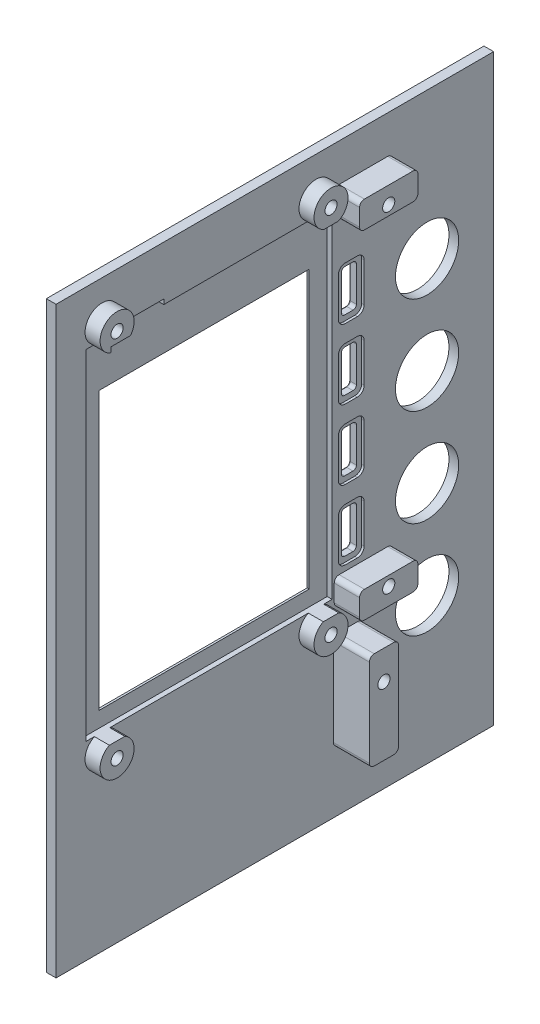
SolidWorks part; units mm, degrees
ref_plane "Front Plane" through (0, 0, 0) normal (0, 0, 1) x (1, 0, 0)
ref_plane "Top Plane" through (0, 0, 0) normal (0, 1, 0) x (1, 0, 0)
ref_plane "Right Plane" through (0, 0, 0) normal (1, 0, 0) x (0, 0, -1)
ref_plane "Plane2" through (-1175.0441, 0, 0) normal (-1, 0, 0) x (0, 0, 1)
sketch "Sketch2" plane through (-1175.0441, 0, 0) normal (-1, 0, 0) x (0, 0, 1)
  line L0 (-1293.9703, -887.0459) -> (-1293.9703, -787.0459) construction
  line L1 (-1208.9703, -777.0459) -> (-1298.9703, -777.0459)
  line L2 (-1208.9703, -777.0459) -> (-1208.9703, -897.0459)
  line L3 (-1208.9703, -897.0459) -> (-1298.9703, -897.0459)
  line L4 (-1298.9703, -777.0459) -> (-1298.9703, -897.0459)
  line L5 (-1293.9703, -887.0459) -> (-1292.4603, -887.0459) construction
  line L6 (-1293.9703, -787.0459) -> (-1292.4603, -787.0459) construction
  circle A0 centre (-1285.2753, -867.0459) radius 6.5
  circle A1 centre (-1285.2753, -847.0459) radius 6.5
  circle A2 centre (-1285.2753, -827.0459) radius 6.5
  circle A3 centre (-1285.2753, -807.0459) radius 6.5
  ellipse E0 centre (-1285.2753, -867.0459) end of major axis (-1284.8157, -867.5055) minor radius 0.65 construction
  ellipse E1 centre (-1285.2753, -847.0459) end of major axis (-1284.8157, -847.5055) minor radius 0.65 construction
  ellipse E2 centre (-1285.2753, -827.0459) end of major axis (-1284.8157, -827.5055) minor radius 0.65 construction
  ellipse E3 centre (-1285.2753, -807.0459) end of major axis (-1284.8157, -807.5055) minor radius 0.65 construction
  ellipse E4 centre (-1285.2753, -867.0459) end of major axis (-1284.8157, -867.5055) minor radius 0.65
  ellipse E5 centre (-1285.2753, -847.0459) end of major axis (-1284.8157, -847.5055) minor radius 0.65 construction
  ellipse E6 centre (-1285.2753, -827.0459) end of major axis (-1284.8157, -827.5055) minor radius 0.65
  ellipse E7 centre (-1285.2753, -807.0459) end of major axis (-1284.8157, -807.5055) minor radius 0.65
  dimension "D5" = 13
  dimension "D6" = 13
  dimension "D7" = 13
  dimension "D8" = 13
  dimension "D1" = 5
  dimension "D2" = 10
  dimension "D3" = 10
  dimension "D4" = 90
extrude "Boss-Extrude2" add sketch "Sketch2" along normal blind 2 contours L1 L4 L3 L2 A3 A2 A1 A0 region at (-1175.0441, -837.0459, -1252.3518)
sketch "Sketch3" plane through (-1177.0441, 0, 0) normal (-1, 0, 0) x (0, 0, 1)
  line L12 (-1218.8332, -854.8056) -> (-1262.0332, -854.8056) construction
  line L13 (-1262.0332, -854.8056) -> (-1262.0332, -797.8256) construction
  line L14 (-1218.8332, -797.8256) -> (-1218.8332, -854.8056) construction
  line L15 (-1262.0332, -797.8256) -> (-1218.8332, -797.8256) construction
  line L16 (-1218.8332, -854.8056) -> (-1262.0332, -854.8056)
  line L17 (-1262.0332, -854.8056) -> (-1262.0332, -797.8256)
  line L18 (-1218.8332, -797.8256) -> (-1218.8332, -854.8056)
  line L19 (-1262.0332, -797.8256) -> (-1218.8332, -797.8256)
extrude "tft_cutout" cut sketch "Sketch3" against normal through all
sketch "tft_inset_cutout" plane through (-1175.0441, 0, 0) normal (1, 0, 0) x (0, 0, -1)
  line L4 (1215.6332, -788.6846) -> (1215.6332, -857.4846) construction
  line L5 (1265.2332, -788.6846) -> (1215.6332, -788.6846) construction
  line L12 (1265.2332, -857.4846) -> (1265.2332, -788.6846) construction
  line L17 (1215.6332, -857.4846) -> (1265.2332, -857.4846) construction
  line L18 (1265.2332, -857.4846) -> (1265.2332, -788.6846) construction
  line L19 (1215.6332, -857.4846) -> (1265.2332, -857.4846) construction
  line L20 (1215.6332, -788.6846) -> (1215.6332, -857.4846) construction
  line L21 (1265.2332, -788.6846) -> (1215.6332, -788.6846) construction
  line L22 (1265.7332, -788.1846) -> (1215.1332, -788.1846)
  line L26 (1217.1332, -788.6846) -> (1231.1332, -788.6846)
  line L27 (1217.1332, -788.6846) -> (1217.1332, -787.1846)
  line L28 (1217.1332, -787.1846) -> (1231.1332, -787.1846)
  line L29 (1231.1332, -788.6846) -> (1231.1332, -787.1846)
  line L30 (1215.1332, -788.1846) -> (1215.1332, -857.9846)
  line L31 (1215.1332, -857.9846) -> (1265.7332, -857.9846)
  line L32 (1265.7332, -857.9846) -> (1265.7332, -788.1846)
  line M40 (1262.0332, -854.8056) -> (1218.8332, -854.8056)
  line M41 (1218.8332, -854.8056) -> (1218.8332, -797.8256)
  line M42 (1218.8332, -797.8256) -> (1262.0332, -797.8256)
  line M43 (1262.0332, -797.8256) -> (1262.0332, -854.8056)
  dimension "D3" = 1.5
  dimension "D4" = 0.5
  dimension "D1" = 14
  dimension "D2" = 1.5
extrude "Cut-Extrude2" cut sketch "tft_inset_cutout" against normal up to surface (1 mm away) contours L18 | L31 L32 L22 L29 L26 L27 L30 M43 M40 M41 M42 | L26 L29 L22 L27 | L22 L29 L28 L27 region at (-1175.0441, -823.0846, -1264.8711) region at (-1175.0441, -788.4346, -1224.1332) region at (-1175.0441, -787.6846, -1224.1332)
chamfer "Chamfer2" distance 1 angle 30 4 edges at (-1177.0441, -826.3156, -1262.0332) (-1177.0441, -854.8056, -1240.4332) (-1177.0441, -826.3156, -1218.8332) (-1177.0441, -797.8256, -1240.4332) first distance on face at (-1177.0441, -826.3156, -1240.4332)
sketch "Sketch6" plane through (-1175.0441, 0, 0) normal (1, 0, 0) x (0, 0, -1)
  line L5 (1266.1832, -859.8139) -> (1278.1832, -859.8139)
  line L6 (1266.1832, -859.8139) -> (1266.1832, -854.3139)
  line L7 (1266.1832, -854.3139) -> (1278.1832, -854.3139)
  line L8 (1266.1832, -859.8139) -> (1278.1832, -859.8139)
  line L9 (1278.1832, -859.8139) -> (1278.1832, -784.8139)
  line L10 (1278.1832, -784.8139) -> (1266.1832, -784.8139)
  line L11 (1266.1832, -784.8139) -> (1266.1832, -859.8139)
  line L12 (1266.1832, -859.8139) -> (1278.1832, -859.8139) construction
  line L13 (1278.1832, -859.8139) -> (1278.1832, -784.8139) construction
  line L14 (1278.1832, -784.8139) -> (1266.1832, -784.8139) construction
  line L15 (1266.1832, -784.8139) -> (1266.1832, -859.8139) construction
  line L16 (1278.1832, -859.8139) -> (1278.1832, -854.3139)
  line L17 (1266.1832, -784.8139) -> (1278.1832, -784.8139)
  line L18 (1266.1832, -784.8139) -> (1266.1832, -790.3139)
  line L19 (1266.1832, -790.3139) -> (1278.1832, -790.3139)
  line L20 (1278.1832, -784.8139) -> (1278.1832, -790.3139)
  circle A0 centre (1272.1832, -856.3139) radius 1.25 construction
  circle A1 centre (1272.1832, -856.3139) radius 1.25 construction
  circle A2 centre (1272.1832, -856.3139) radius 1.25
  circle A3 centre (1272.1832, -788.3139) radius 1.25 construction
  circle A4 centre (1272.1832, -788.3139) radius 1.25 construction
  circle A5 centre (1272.1832, -788.3139) radius 1.25
  dimension "D2" = 2.5
  dimension "D4" = 2.5
  dimension "D3" = 2
  dimension "D5" = 2
extrude "menu_standoffs" add sketch "Sketch6" along normal up to surface (5.203 mm away)
fillet "Fillet1" radius 1 8 edges at (-1172.4426, -790.3139, -1266.1832) (-1172.4426, -790.3139, -1278.1832) (-1172.4426, -784.8139, -1278.1832) (-1172.4426, -784.8139, -1266.1832) (-1172.4426, -854.3139, -1278.1832) (-1172.4426, -854.3139, -1266.1832) (-1172.4426, -859.8139, -1266.1832) (-1172.4426, -859.8139, -1278.1832)
sketch "Sketch7" plane through (-1169.8411, 0, 0) normal (1, 0, 0) x (0, 0, -1)
  circle A0 centre (1272.1832, -856.3139) radius 1.25 construction
  circle A1 centre (1272.1832, -788.3139) radius 1.25 construction
  circle A2 centre (1272.1832, -856.3139) radius 1.25
  circle A3 centre (1272.1832, -788.3139) radius 1.25
extrude "menu_standoff_holes" [suppressed] cut sketch "Sketch7" against normal blind 5 contours A2
sketch "Sketch8" plane through (-1175.0441, 0, 0) normal (1, 0, 0) x (0, 0, -1)
  circle A0 centre (1218.4332, -861.1056) radius 1.55 construction
  circle A1 centre (1262.4332, -861.1056) radius 1.55 construction
  circle A2 centre (1262.4332, -785.0256) radius 1.55 construction
  circle A3 centre (1218.4332, -785.0258) radius 1.55 construction
  circle A4 centre (1218.4332, -861.1056) radius 1.55 construction
  circle A5 centre (1262.4332, -861.1056) radius 1.55 construction
  circle A6 centre (1262.4332, -785.0256) radius 1.55 construction
  circle A7 centre (1218.4332, -785.0258) radius 1.55 construction
  circle A8 centre (1218.4332, -785.0258) radius 3.5
  circle A9 centre (1262.4332, -785.0256) radius 3.5
  circle A10 centre (1262.4332, -861.1056) radius 3.5
  circle A11 centre (1218.4332, -861.1056) radius 3.5
  circle A12 centre (1218.4332, -785.0258) radius 1.25
  circle A13 centre (1218.4332, -861.1056) radius 1.25
  circle A14 centre (1262.4332, -861.1056) radius 1.25
  circle A15 centre (1262.4332, -785.0256) radius 1.25
  dimension "D2" = 2.5
  dimension "D1" = 7
extrude "TFT_standoffs" add sketch "Sketch8" along normal up to surface (3.09 mm away)
sketch "Sketch9" plane through (-1175.0441, 0, 0) normal (1, 0, 0) x (0, 0, -1)
  circle A0 centre (1218.4332, -785.0258) radius 1.25 construction
  circle A1 centre (1218.4332, -861.1056) radius 1.25 construction
  circle A2 centre (1262.4332, -861.1056) radius 1.25 construction
  circle A3 centre (1262.4332, -785.0256) radius 1.25 construction
  circle A4 centre (1218.4332, -785.0258) radius 1.25
  circle A5 centre (1218.4332, -861.1056) radius 1.25
  circle A6 centre (1262.4332, -861.1056) radius 1.25
  circle A7 centre (1262.4332, -785.0256) radius 1.25
extrude "TFT_standoff_holes" cut sketch "Sketch9" against normal offset from surface (1 mm away) 1 up to face at (-1177.0441, -826.3156, -1240.4332)
extrude "Cut-Extrude5" cut sketch "Sketch5<3>" along normal through all contours L31 L32 L22 L29 L26 L27 L30 M43 M40 M41 M42 | L22 L29 L28 L27 | L26 L29 L22 L27 region at (-1175.0441, -823.0846, -1264.8711) region at (-1175.0441, -788.4346, -1224.1332) region at (-1175.0441, -787.6846, -1224.1332)
sketch "Sketch5<3>" plane through (-1175.0441, 0, 0) normal (1, 0, 0) x (0, 0, -1) same geometry as "tft_inset_cutout"
sketch "Sketch10" plane through (-1175.0441, 0, 0) normal (1, 0, 0) x (0, 0, -1)
  line L0 (1271.9367, -800.8206) -> (1271.9367, -808.8206) construction
  line L1 (1270.9367, -809.8206) -> (1268.4367, -809.8206) construction
  line L2 (1267.4367, -808.8206) -> (1267.4367, -800.8206) construction
  line L3 (1268.4367, -799.8206) -> (1270.9367, -799.8206) construction
  line L4 (1271.9367, -800.8206) -> (1271.9367, -808.8206) construction
  line L5 (1270.9367, -809.8206) -> (1268.4367, -809.8206) construction
  line L6 (1267.4367, -808.8206) -> (1267.4367, -800.8206) construction
  line L7 (1268.4367, -799.8206) -> (1270.9367, -799.8206) construction
  line L8 (1272.3367, -800.8206) -> (1272.3367, -808.8206)
  line L9 (1270.9367, -810.2206) -> (1268.4367, -810.2206)
  line L10 (1267.0367, -808.8206) -> (1267.0367, -800.8206)
  line L11 (1268.4367, -799.4206) -> (1270.9367, -799.4206)
  line L12 (1272.3367, -815.1506) -> (1272.3367, -823.1506)
  line L13 (1270.9367, -824.5506) -> (1268.4367, -824.5506)
  line L14 (1267.0367, -823.1506) -> (1267.0367, -815.1506)
  line L15 (1268.4367, -813.7506) -> (1270.9367, -813.7506)
  line L16 (1271.9367, -815.1506) -> (1271.9367, -823.1506) construction
  line L17 (1270.9367, -824.1506) -> (1268.4367, -824.1506) construction
  line L18 (1267.4367, -823.1506) -> (1267.4367, -815.1506) construction
  line L19 (1268.4367, -814.1506) -> (1270.9367, -814.1506) construction
  line L20 (1272.3367, -829.4806) -> (1272.3367, -837.4806)
  line L21 (1270.9367, -838.8806) -> (1268.4367, -838.8806)
  line L22 (1267.0367, -837.4806) -> (1267.0367, -829.4806)
  line L23 (1268.4367, -828.0806) -> (1270.9367, -828.0806)
  line L24 (1271.9367, -829.4806) -> (1271.9367, -837.4806) construction
  line L25 (1270.9367, -838.4806) -> (1268.4367, -838.4806) construction
  line L26 (1267.4367, -837.4806) -> (1267.4367, -829.4806) construction
  line L27 (1268.4367, -828.4806) -> (1270.9367, -828.4806) construction
  line L28 (1272.3367, -843.8106) -> (1272.3367, -851.8106)
  line L29 (1270.9367, -853.2106) -> (1268.4367, -853.2106)
  line L30 (1267.0367, -851.8106) -> (1267.0367, -843.8106)
  line L31 (1268.4367, -842.4106) -> (1270.9367, -842.4106)
  line L32 (1271.9367, -843.8106) -> (1271.9367, -851.8106) construction
  line L33 (1270.9367, -852.8106) -> (1268.4367, -852.8106) construction
  line L34 (1267.4367, -851.8106) -> (1267.4367, -843.8106) construction
  line L35 (1268.4367, -842.8106) -> (1270.9367, -842.8106) construction
  arc A0 (1271.9367, -800.8206) -> (1270.9367, -799.8206) centre (1270.9367, -800.8206) ccw construction
  arc A1 (1270.9367, -809.8206) -> (1271.9367, -808.8206) centre (1270.9367, -808.8206) ccw construction
  arc A2 (1267.4367, -808.8206) -> (1268.4367, -809.8206) centre (1268.4367, -808.8206) ccw construction
  arc A3 (1268.4367, -799.8206) -> (1267.4367, -800.8206) centre (1268.4367, -800.8206) ccw construction
  arc A4 (1271.9367, -800.8206) -> (1270.9367, -799.8206) centre (1270.9367, -800.8206) ccw construction
  arc A5 (1270.9367, -809.8206) -> (1271.9367, -808.8206) centre (1270.9367, -808.8206) ccw construction
  arc A6 (1267.4367, -808.8206) -> (1268.4367, -809.8206) centre (1268.4367, -808.8206) ccw construction
  arc A7 (1268.4367, -799.8206) -> (1267.4367, -800.8206) centre (1268.4367, -800.8206) ccw construction
  arc A8 (1270.9367, -810.2206) -> (1272.3367, -808.8206) centre (1270.9367, -808.8206) ccw
  arc A9 (1267.0367, -808.8206) -> (1268.4367, -810.2206) centre (1268.4367, -808.8206) ccw
  arc A10 (1268.4367, -799.4206) -> (1267.0367, -800.8206) centre (1268.4367, -800.8206) ccw
  arc A11 (1272.3367, -800.8206) -> (1270.9367, -799.4206) centre (1270.9367, -800.8206) ccw
  arc A12 (1270.9367, -824.5506) -> (1272.3367, -823.1506) centre (1270.9367, -823.1506) ccw
  arc A13 (1267.0367, -823.1506) -> (1268.4367, -824.5506) centre (1268.4367, -823.1506) ccw
  arc A14 (1268.4367, -813.7506) -> (1267.0367, -815.1506) centre (1268.4367, -815.1506) ccw
  arc A15 (1272.3367, -815.1506) -> (1270.9367, -813.7506) centre (1270.9367, -815.1506) ccw
  arc A16 (1271.9367, -815.1506) -> (1270.9367, -814.1506) centre (1270.9367, -815.1506) ccw construction
  arc A17 (1270.9367, -824.1506) -> (1271.9367, -823.1506) centre (1270.9367, -823.1506) ccw construction
  arc A18 (1267.4367, -823.1506) -> (1268.4367, -824.1506) centre (1268.4367, -823.1506) ccw construction
  arc A19 (1268.4367, -814.1506) -> (1267.4367, -815.1506) centre (1268.4367, -815.1506) ccw construction
  arc A20 (1270.9367, -838.8806) -> (1272.3367, -837.4806) centre (1270.9367, -837.4806) ccw
  arc A21 (1267.0367, -837.4806) -> (1268.4367, -838.8806) centre (1268.4367, -837.4806) ccw
  arc A22 (1268.4367, -828.0806) -> (1267.0367, -829.4806) centre (1268.4367, -829.4806) ccw
  arc A23 (1272.3367, -829.4806) -> (1270.9367, -828.0806) centre (1270.9367, -829.4806) ccw
  arc A24 (1271.9367, -829.4806) -> (1270.9367, -828.4806) centre (1270.9367, -829.4806) ccw construction
  arc A25 (1270.9367, -838.4806) -> (1271.9367, -837.4806) centre (1270.9367, -837.4806) ccw construction
  arc A26 (1267.4367, -837.4806) -> (1268.4367, -838.4806) centre (1268.4367, -837.4806) ccw construction
  arc A27 (1268.4367, -828.4806) -> (1267.4367, -829.4806) centre (1268.4367, -829.4806) ccw construction
  arc A28 (1270.9367, -853.2106) -> (1272.3367, -851.8106) centre (1270.9367, -851.8106) ccw
  arc A29 (1267.0367, -851.8106) -> (1268.4367, -853.2106) centre (1268.4367, -851.8106) ccw
  arc A30 (1268.4367, -842.4106) -> (1267.0367, -843.8106) centre (1268.4367, -843.8106) ccw
  arc A31 (1272.3367, -843.8106) -> (1270.9367, -842.4106) centre (1270.9367, -843.8106) ccw
  arc A32 (1271.9367, -843.8106) -> (1270.9367, -842.8106) centre (1270.9367, -843.8106) ccw construction
  arc A33 (1270.9367, -852.8106) -> (1271.9367, -851.8106) centre (1270.9367, -851.8106) ccw construction
  arc A34 (1267.4367, -851.8106) -> (1268.4367, -852.8106) centre (1268.4367, -851.8106) ccw construction
  arc A35 (1268.4367, -842.8106) -> (1267.4367, -843.8106) centre (1268.4367, -843.8106) ccw construction
  dimension "D1" = 0.4
  dimension "D2" = 4
extrude "Cut-Extrude6" cut sketch "Sketch10" against normal offset from surface 1.5 and the other way through all up to face at (-1177.0441, -826.3156, -1240.4332)
sketch "Sketch11" plane through (-1177.0441, 0, 0) normal (-1, 0, 0) x (0, 0, 1)
  line L0 (-1270.5367, -808.8206) -> (-1268.8367, -808.8206) construction
  line L1 (-1270.9367, -801.2206) -> (-1270.9367, -808.4206) construction
  line L2 (-1270.5367, -800.8206) -> (-1268.8367, -800.8206) construction
  line L3 (-1268.4367, -801.2206) -> (-1268.4367, -808.4206) construction
  line L4 (-1270.5367, -808.8206) -> (-1268.8367, -808.8206) construction
  line L5 (-1270.9367, -801.2206) -> (-1270.9367, -808.4206) construction
  line L6 (-1270.5367, -800.8206) -> (-1268.8367, -800.8206) construction
  line L7 (-1268.4367, -801.2206) -> (-1268.4367, -808.4206) construction
  line L8 (-1268.1367, -801.2206) -> (-1268.1367, -808.4206)
  line L9 (-1270.5367, -809.1206) -> (-1268.8367, -809.1206)
  line L10 (-1271.2367, -801.2206) -> (-1271.2367, -808.4206)
  line L11 (-1270.5367, -800.5206) -> (-1268.8367, -800.5206)
  line L12 (-1268.1367, -815.5506) -> (-1268.1367, -822.7506)
  line L13 (-1270.5367, -823.4506) -> (-1268.8367, -823.4506)
  line L14 (-1271.2367, -815.5506) -> (-1271.2367, -822.7506)
  line L15 (-1270.5367, -814.8506) -> (-1268.8367, -814.8506)
  line L16 (-1270.5367, -823.1506) -> (-1268.8367, -823.1506) construction
  line L17 (-1270.9367, -815.5506) -> (-1270.9367, -822.7506) construction
  line L18 (-1270.5367, -815.1506) -> (-1268.8367, -815.1506) construction
  line L19 (-1268.4367, -815.5506) -> (-1268.4367, -822.7506) construction
  line L20 (-1268.1367, -829.8806) -> (-1268.1367, -837.0806)
  line L21 (-1270.5367, -837.7806) -> (-1268.8367, -837.7806)
  line L22 (-1271.2367, -829.8806) -> (-1271.2367, -837.0806)
  line L23 (-1270.5367, -829.1806) -> (-1268.8367, -829.1806)
  line L24 (-1270.5367, -837.4806) -> (-1268.8367, -837.4806) construction
  line L25 (-1270.9367, -829.8806) -> (-1270.9367, -837.0806) construction
  line L26 (-1270.5367, -829.4806) -> (-1268.8367, -829.4806) construction
  line L27 (-1268.4367, -829.8806) -> (-1268.4367, -837.0806) construction
  line L28 (-1268.1367, -844.2106) -> (-1268.1367, -851.4106)
  line L29 (-1270.5367, -852.1106) -> (-1268.8367, -852.1106)
  line L30 (-1271.2367, -844.2106) -> (-1271.2367, -851.4106)
  line L31 (-1270.5367, -843.5106) -> (-1268.8367, -843.5106)
  line L32 (-1270.5367, -851.8106) -> (-1268.8367, -851.8106) construction
  line L33 (-1270.9367, -844.2106) -> (-1270.9367, -851.4106) construction
  line L34 (-1270.5367, -843.8106) -> (-1268.8367, -843.8106) construction
  line L35 (-1268.4367, -844.2106) -> (-1268.4367, -851.4106) construction
  arc A0 (-1268.8367, -808.8206) -> (-1268.4367, -808.4206) centre (-1268.8367, -808.4206) ccw construction
  arc A1 (-1270.9367, -808.4206) -> (-1270.5367, -808.8206) centre (-1270.5367, -808.4206) ccw construction
  arc A2 (-1270.5367, -800.8206) -> (-1270.9367, -801.2206) centre (-1270.5367, -801.2206) ccw construction
  arc A3 (-1268.4367, -801.2206) -> (-1268.8367, -800.8206) centre (-1268.8367, -801.2206) ccw construction
  arc A4 (-1268.8367, -808.8206) -> (-1268.4367, -808.4206) centre (-1268.8367, -808.4206) ccw construction
  arc A5 (-1270.9367, -808.4206) -> (-1270.5367, -808.8206) centre (-1270.5367, -808.4206) ccw construction
  arc A6 (-1270.5367, -800.8206) -> (-1270.9367, -801.2206) centre (-1270.5367, -801.2206) ccw construction
  arc A7 (-1268.4367, -801.2206) -> (-1268.8367, -800.8206) centre (-1268.8367, -801.2206) ccw construction
  arc A8 (-1268.8367, -809.1206) -> (-1268.1367, -808.4206) centre (-1268.8367, -808.4206) ccw
  arc A9 (-1271.2367, -808.4206) -> (-1270.5367, -809.1206) centre (-1270.5367, -808.4206) ccw
  arc A10 (-1270.5367, -800.5206) -> (-1271.2367, -801.2206) centre (-1270.5367, -801.2206) ccw
  arc A11 (-1268.1367, -801.2206) -> (-1268.8367, -800.5206) centre (-1268.8367, -801.2206) ccw
  arc A12 (-1268.8367, -823.4506) -> (-1268.1367, -822.7506) centre (-1268.8367, -822.7506) ccw
  arc A13 (-1271.2367, -822.7506) -> (-1270.5367, -823.4506) centre (-1270.5367, -822.7506) ccw
  arc A14 (-1270.5367, -814.8506) -> (-1271.2367, -815.5506) centre (-1270.5367, -815.5506) ccw
  arc A15 (-1268.1367, -815.5506) -> (-1268.8367, -814.8506) centre (-1268.8367, -815.5506) ccw
  arc A16 (-1268.8367, -823.1506) -> (-1268.4367, -822.7506) centre (-1268.8367, -822.7506) ccw construction
  arc A17 (-1270.9367, -822.7506) -> (-1270.5367, -823.1506) centre (-1270.5367, -822.7506) ccw construction
  arc A18 (-1270.5367, -815.1506) -> (-1270.9367, -815.5506) centre (-1270.5367, -815.5506) ccw construction
  arc A19 (-1268.4367, -815.5506) -> (-1268.8367, -815.1506) centre (-1268.8367, -815.5506) ccw construction
  arc A20 (-1268.8367, -837.7806) -> (-1268.1367, -837.0806) centre (-1268.8367, -837.0806) ccw
  arc A21 (-1271.2367, -837.0806) -> (-1270.5367, -837.7806) centre (-1270.5367, -837.0806) ccw
  arc A22 (-1270.5367, -829.1806) -> (-1271.2367, -829.8806) centre (-1270.5367, -829.8806) ccw
  arc A23 (-1268.1367, -829.8806) -> (-1268.8367, -829.1806) centre (-1268.8367, -829.8806) ccw
  arc A24 (-1268.8367, -837.4806) -> (-1268.4367, -837.0806) centre (-1268.8367, -837.0806) ccw construction
  arc A25 (-1270.9367, -837.0806) -> (-1270.5367, -837.4806) centre (-1270.5367, -837.0806) ccw construction
  arc A26 (-1270.5367, -829.4806) -> (-1270.9367, -829.8806) centre (-1270.5367, -829.8806) ccw construction
  arc A27 (-1268.4367, -829.8806) -> (-1268.8367, -829.4806) centre (-1268.8367, -829.8806) ccw construction
  arc A28 (-1268.8367, -852.1106) -> (-1268.1367, -851.4106) centre (-1268.8367, -851.4106) ccw
  arc A29 (-1271.2367, -851.4106) -> (-1270.5367, -852.1106) centre (-1270.5367, -851.4106) ccw
  arc A30 (-1270.5367, -843.5106) -> (-1271.2367, -844.2106) centre (-1270.5367, -844.2106) ccw
  arc A31 (-1268.1367, -844.2106) -> (-1268.8367, -843.5106) centre (-1268.8367, -844.2106) ccw
  arc A32 (-1268.8367, -851.8106) -> (-1268.4367, -851.4106) centre (-1268.8367, -851.4106) ccw construction
  arc A33 (-1270.9367, -851.4106) -> (-1270.5367, -851.8106) centre (-1270.5367, -851.4106) ccw construction
  arc A34 (-1270.5367, -843.8106) -> (-1270.9367, -844.2106) centre (-1270.5367, -844.2106) ccw construction
  arc A35 (-1268.4367, -844.2106) -> (-1268.8367, -843.8106) centre (-1268.8367, -844.2106) ccw construction
  dimension "D1" = 0.3
  dimension "D2" = 4
extrude "Cut-Extrude7" cut sketch "Sketch11" against normal through all
fillet "Fillet2" radius 0.25 32 edges at (-1177.0441, -804.8206, -1268.1367) (-1177.0441, -808.9155, -1268.3418) (-1177.0441, -809.1206, -1269.6867) (-1177.0441, -808.9155, -1271.0317) (-1177.0441, -804.8206, -1271.2367) (-1177.0441, -800.7256, -1271.0317) (-1177.0441, -800.5206, -1269.6867) (-1177.0441, -823.4506, -1269.6867) (-1177.0441, -823.2455, -1271.0317) (-1177.0441, -819.1506, -1271.2367) (-1177.0441, -815.0556, -1271.0317) (-1177.0441, -814.8506, -1269.6867) (-1177.0441, -815.0556, -1268.3418) (-1177.0441, -819.1506, -1268.1367) (-1177.0441, -837.7806, -1269.6867) (-1177.0441, -837.5755, -1271.0317) (-1177.0441, -833.4806, -1271.2367) (-1177.0441, -829.3856, -1271.0317) (-1177.0441, -829.1806, -1269.6867) (-1177.0441, -829.3856, -1268.3418) (-1177.0441, -833.4806, -1268.1367) (-1177.0441, -847.8106, -1268.1367) (-1177.0441, -851.9055, -1268.3418) (-1177.0441, -852.1106, -1269.6867) (-1177.0441, -851.9055, -1271.0317) (-1177.0441, -847.8106, -1271.2367) (-1177.0441, -843.7156, -1271.0317) (-1177.0441, -843.5106, -1269.6867) (-1177.0441, -800.7256, -1268.3418) (-1177.0441, -823.2455, -1268.3418) (-1177.0441, -837.5755, -1268.3418) (-1177.0441, -843.7156, -1268.3418)
sketch "Sketch12" plane through (-1175.0441, 0, 0) normal (1, 0, 0) x (0, 0, -1)
  line L0 (1271.9795, -884.5779) -> (1211.9795, -884.5779) construction
  line L1 (1271.9795, -864.5779) -> (1265.9795, -864.5779)
  line L2 (1271.9795, -864.5779) -> (1271.9795, -884.5779)
  line L3 (1271.9795, -884.5779) -> (1265.9795, -884.5779)
  line L4 (1265.9795, -864.5779) -> (1265.9795, -884.5779)
  circle A0 centre (1268.9795, -870.5779) radius 1.25
  dimension "D2" = 2.5
  dimension "D1" = 6
extrude "selector_standoffs" add sketch "Sketch12" along normal up to surface (7.4271 mm away)
fillet "Fillet3" radius 1 4 edges at (-1171.3306, -884.5779, -1271.9795) (-1171.3306, -864.5779, -1271.9795) (-1171.3306, -864.5779, -1265.9795) (-1171.3306, -884.5779, -1265.9795)
equation "\"R_BNC\"= 13"
equation "\"D8@Sketch2\"=\"R_BNC\""
equation "\"D7@Sketch2\"=\"R_BNC\""
equation "\"D6@Sketch2\"=\"R_BNC\""
equation "\"D5@Sketch2\"=\"R_BNC\""
equation "\"R_m3_TAP\"= 2.5"
equation "\"D2@Sketch6\"=\"R_m3_TAP\""
equation "\"D4@Sketch6\"=\"R_m3_TAP\""
equation "\"R_TFT_mount_outer\"= 7"
equation "\"D1@Sketch8\"=\"R_TFT_mount_outer\""
equation "\"D2@Sketch8\"=\"R_m3_TAP\""
equation "\"D2@Sketch12\"=\"R_m3_TAP\""
